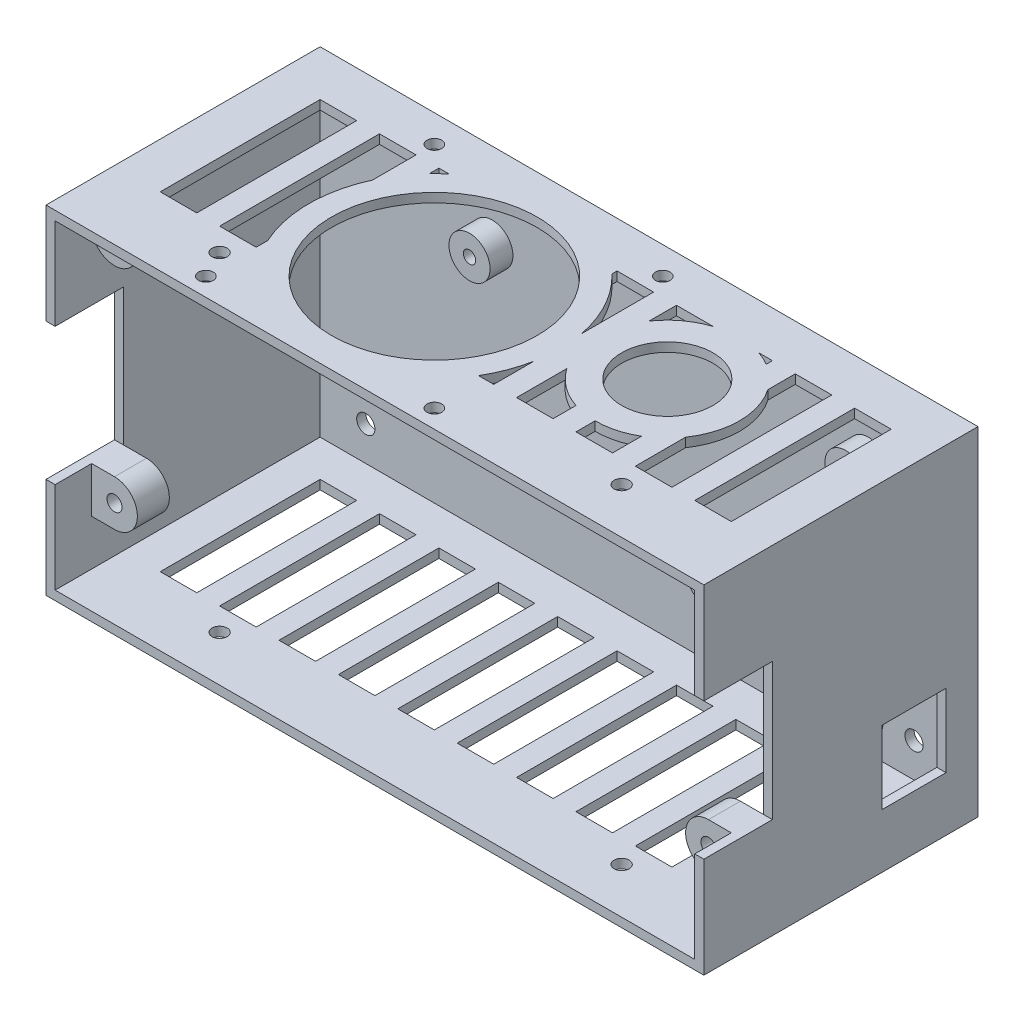
SolidWorks part; units mm, degrees
note: The reader was unsure of these and kept them because the rebuilt part matched: shared geometry of "Esboço8<3>", "Esboço13<3>", "Esboço15<3>".
material "ABS"
ref_plane "Plano frontal" through (0, 0, 0) normal (0, 0, 1) x (1, 0, 0)
ref_plane "Plano superior" through (0, 0, 0) normal (0, 1, 0) x (1, 0, 0)
ref_plane "Plano direito" through (0, 0, 0) normal (1, 0, 0) x (0, 0, -1)
sketch "Esboço1" plane through (0, 0, 0) normal (0, 0, 1) x (1, 0, 0)
  line L0 (-72, 37) -> (72, 37)
  line L1 (-70, 35) -> (70, 35)
  line L2 (-70, 35) -> (-70, -35)
  line L3 (-70, -35) -> (70, -35)
  line L4 (70, 35) -> (70, -35)
  line L5 (-70, 35) -> (70, -35) construction
  line L6 (-70, -35) -> (70, 35) construction
  line L7 (72, 37) -> (72, -37)
  line L8 (-72, -37) -> (72, -37)
  line L9 (-72, 37) -> (-72, -37)
  point P0 (0, 0)
  dimension "D2" = 140
  dimension "D3" = 70
  dimension "D1" = 2
extrude "Ressalto-extrusão1" add sketch "Esboço1" along normal blind 60
sketch "Esboço2" plane through (0, 0, 0) normal (0, 0, -1) x (-1, 0, 0)
  line L0 (-72, -37) -> (-72, 37) construction
  line L1 (72, -37) -> (-72, -37) construction
  line L2 (-72, 37) -> (72, 37) construction
  line L3 (72, 37) -> (72, -37) construction
  line L4 (-72, -37) -> (-72, 37)
  line L5 (72, -37) -> (-72, -37)
  line L6 (-72, 37) -> (72, 37)
  line L7 (72, 37) -> (72, -37)
  line L8 (60, 27.5) -> (-60, 27.5) construction
  line L9 (-60, 27.5) -> (-60, -27.5) construction
  line L10 (-60, -27.5) -> (60, -27.5) construction
  line L11 (60, -27.5) -> (60, 27.5) construction
  line L12 (-70, -35) -> (-70, 35) construction
  line L13 (70, -35) -> (-70, -35) construction
  circle A0 centre (-60, -27.5) radius 2
  circle A1 centre (60, -27.5) radius 2
  circle A2 centre (60, 27.5) radius 2
  circle A3 centre (-60, 27.5) radius 2
  point P12 (0, 27.5)
  point P13 (0, 37)
  point P14 (-60, 0)
  point P15 (-72, 0)
  dimension "D1" = 4
  dimension "D2" = 10
  dimension "D3" = 7.5
extrude "Ressalto-extrusão2" add sketch "Esboço2" against normal blind 2
sketch "Esboço3" plane through (72, 0, 0) normal (1, 0, 0) x (0, 0, -1)
  line L0 (-60, -37) -> (0, -37) construction
  line L5 (-21, -9.1) -> (-7, -9.1)
  line L6 (-21, -9.1) -> (-21, -25.1)
  line L7 (-21, -25.1) -> (-7, -25.1)
  line L8 (-7, -9.1) -> (-7, -25.1)
  line L18 (0, -37) -> (0, 37) construction
  dimension "D1" = 16
  dimension "D2" = 14
  dimension "D3" = 11.9
  dimension "D4" = 7
extrude "USB + fonte" cut sketch "Esboço3" against normal blind 10
sketch "Esboço6" plane through (0, -37, 0) normal (0, -1, 0) x (1, 0, 0)
  line L0 (-72, 0) -> (72, 0) construction
  line L1 (-62, 45) -> (-54, 45)
  line L2 (-62, 45) -> (-62, 10)
  line L3 (-62, 10) -> (-54, 10)
  line L4 (-54, 45) -> (-54, 10)
  line L5 (-72, 60) -> (-72, 0) construction
  line L6 (-49, 45) -> (-41, 45)
  line L7 (-49, 45) -> (-49, 10)
  line L8 (-49, 10) -> (-41, 10)
  line L9 (-41, 45) -> (-41, 10)
  line L10 (-36, 45) -> (-28, 45)
  line L11 (-36, 45) -> (-36, 10)
  line L12 (-36, 10) -> (-28, 10)
  line L13 (-28, 45) -> (-28, 10)
  line L14 (-23, 45) -> (-15, 45)
  line L15 (-23, 45) -> (-23, 10)
  line L16 (-23, 10) -> (-15, 10)
  line L17 (-15, 45) -> (-15, 10)
  line L18 (-10, 45) -> (-2, 45)
  line L19 (-10, 45) -> (-10, 10)
  line L20 (-10, 10) -> (-2, 10)
  line L21 (-2, 45) -> (-2, 10)
  line L22 (3, 45) -> (11, 45)
  line L23 (3, 45) -> (3, 10)
  line L24 (3, 10) -> (11, 10)
  line L25 (11, 45) -> (11, 10)
  line L26 (16, 45) -> (24, 45)
  line L27 (16, 45) -> (16, 10)
  line L28 (16, 10) -> (24, 10)
  line L29 (24, 45) -> (24, 10)
  line L30 (29, 45) -> (37, 45)
  line L31 (29, 45) -> (29, 10)
  line L32 (29, 10) -> (37, 10)
  line L33 (37, 45) -> (37, 10)
  line L34 (72, 60) -> (72, 0) construction
  line L35 (-72, 60) -> (-72, 0) construction
  line L36 (-72, 60) -> (72, 60) construction
  line L37 (42, 45) -> (50, 45)
  line L38 (42, 45) -> (42, 10)
  line L39 (42, 10) -> (50, 10)
  line L40 (50, 45) -> (50, 10)
  line L41 (55, 45) -> (63, 45)
  line L42 (55, 45) -> (55, 10)
  line L43 (55, 10) -> (63, 10)
  line L44 (63, 45) -> (63, 10)
  circle A0 centre (-44, 50) radius 1.65
  circle A1 centre (44, 50) radius 1.65
  dimension "D8" = 3.3
  dimension "D1" = 8
  dimension "D2" = 35
  dimension "D4" = 10
  dimension "D3" = 10
  dimension "D6" = 28
  dimension "D7" = 28
  dimension "D9" = 10
  dimension "D5" = 10
extrude "saida de ar" cut sketch "Esboço6" against normal through all both and the other way through all
sketch "Esboço7" plane through (-72, 0, 0) normal (-1, 0, 0) x (0, 0, 1)
  line L0 (60, 37) -> (60, -37) construction
  line L1 (45, -15) -> (60, -15)
  line L2 (45, -15) -> (45, 15)
  line L3 (45, 15) -> (60, 15)
  line L4 (60, -15) -> (60, 15)
  line L5 (45, -15) -> (60, 15) construction
  line L6 (45, 15) -> (60, -15) construction
  point P0 (52.5, 0)
  point P7 (0, 0)
  dimension "D1" = 30
  dimension "D2" = 15
extrude "display" cut sketch "Esboço7" against normal through all
sketch "Esboço8" plane through (0, 0, 2) normal (0, 0, -1) x (-1, 0, 0)
  line L0 (-70, -35) -> (-70, 35) construction
  line L1 (-70, 35) -> (70, 35) construction
  circle A0 centre (-48.7, -27.67) radius 4.5
  circle A1 centre (-48.7, -27.67) radius 1.35
  circle A2 centre (32.3, 20.5) radius 4.5
  circle A3 centre (32.3, 20.5) radius 1.35
  circle A4 centre (-50, 20.5) radius 1.35
  circle A5 centre (-50, 20.5) radius 1.35
  circle A6 centre (-50, 20.5) radius 4.5
  dimension "D1" = 9
  dimension "D2" = 2.7
  dimension "D3" = 82.3
  dimension "D4" = 48.17
  dimension "D5" = 1.3
  dimension "D6" = 20
  dimension "D7" = 14.5
extrude "Ressalto-extrusão3" add sketch "Esboço8" against normal blind 5 contours A2 A3 | A6 A4 | A0 A1
extrude "Corte-extrusão4" cut sketch "Esboço8<3>" along normal through all contours A4 | A3 | A1
sketch "Esboço8<3>" plane through (0, 0, 2) normal (0, 0, -1) x (-1, 0, 0) same geometry as "Esboço8"
sketch "Esboço9" plane through (0, 0, 2) normal (0, 0, 1) x (1, 0, 0)
  circle A0 centre (50, 20.5) radius 3
  circle A1 centre (48.7, -27.67) radius 3
  circle A2 centre (-32.3, 20.5) radius 3
  circle A3 centre (48.7, -27.67) radius 1.35 construction
  dimension "D1" = 6
extrude "Corte-extrusão5" cut sketch "Esboço9" along normal offset from surface 3 and the other way blind 10 up to face at (-27.8, 20.5, 7)
sketch "Esboço11" plane through (0, 0, 60) normal (0, 0, 1) x (1, 0, 0)
  line L0 (-70, 35) -> (-70, 15) construction
  line L1 (70, -25) -> (65, -25)
  line L2 (70, -25) -> (70, -15)
  line L3 (70, 35) -> (65, 35)
  line L4 (-70, -25) -> (-70, -15)
  line L5 (70, -25) -> (-70, 35) construction
  line L6 (70, 35) -> (-70, -25) construction
  line L7 (-72, 37) -> (-72, 15) construction
  line L8 (65, 30) -> (-65, 30) construction
  line L9 (65, 30) -> (65, -20) construction
  line L10 (65, -20) -> (-65, -20) construction
  line L11 (-65, 30) -> (-65, -20) construction
  line L12 (65, 30) -> (-65, -20) construction
  line L13 (65, -20) -> (-65, 30) construction
  line L14 (72, 37) -> (-72, 37) construction
  line L15 (-65, 35) -> (-70, 35)
  line L16 (-70, 30) -> (-70, 35)
  line L17 (70, 30) -> (70, 35)
  line L18 (-65, -25) -> (-70, -25)
  line L19 (70, -35) -> (70, -15) construction
  line L20 (-65, -15) -> (-70, -15)
  line L21 (-70, 35) -> (-70, -35) construction
  line L22 (65, -15) -> (70, -15)
  line L23 (70, -35) -> (70, 35) construction
  arc A0 (-70, 30) -> (-65, 35) centre (-65, 30) ccw
  circle A1 centre (-65, 30) radius 1.65
  arc A2 (65, 35) -> (70, 30) centre (65, 30) ccw
  circle A3 centre (65, 30) radius 1.65
  circle A5 centre (65, -20) radius 1.65
  arc A6 (-65, -25) -> (-65, -15) centre (-65, -20) ccw
  circle A7 centre (-65, -20) radius 1.65
  arc A8 (65, -15) -> (65, -25) centre (65, -20) ccw
  point P0 (0, 0)
  point P10 (0, 0)
  dimension "D3" = 3.3
  dimension "D1" = 7
  dimension "D2" = 7
  dimension "D5" = 50
  dimension "D4" = 5
extrude "Ressalto-extrusão4" add sketch "Esboço11" against normal blind 7 from offset 8 offset against normal yes
sketch "Esboço12" plane through (0, 0, 45) normal (0, 0, -1) x (-1, 0, 0)
  line L1 (-61.8246, 30) -> (-63.4123, 32.75)
  line L2 (-63.4123, 32.75) -> (-66.5877, 32.75)
  line L3 (-66.5877, 32.75) -> (-68.1754, 30)
  line L4 (-68.1754, 30) -> (-66.5877, 27.25)
  line L5 (-66.5877, 27.25) -> (-63.4123, 27.25)
  line L6 (-63.4123, 27.25) -> (-61.8246, 30)
  line L7 (61.8246, 30) -> (63.4123, 27.25)
  line L8 (63.4123, 27.25) -> (66.5877, 27.25)
  line L9 (66.5877, 27.25) -> (68.1754, 30)
  line L10 (68.1754, 30) -> (66.5877, 32.75)
  line L11 (66.5877, 32.75) -> (63.4123, 32.75)
  line L12 (63.4123, 32.75) -> (61.8246, 30)
  line L13 (-61.8246, -20) -> (-63.4123, -17.25)
  line L14 (-63.4123, -17.25) -> (-66.5877, -17.25)
  line L15 (-66.5877, -17.25) -> (-68.1754, -20)
  line L16 (-68.1754, -20) -> (-66.5877, -22.75)
  line L17 (-66.5877, -22.75) -> (-63.4123, -22.75)
  line L18 (-63.4123, -22.75) -> (-61.8246, -20)
  line L19 (61.8246, -20) -> (63.4123, -22.75)
  line L20 (63.4123, -22.75) -> (66.5877, -22.75)
  line L21 (66.5877, -22.75) -> (68.1754, -20)
  line L22 (68.1754, -20) -> (66.5877, -17.25)
  line L23 (66.5877, -17.25) -> (63.4123, -17.25)
  line L24 (63.4123, -17.25) -> (61.8246, -20)
  circle A0 centre (-65, 30) radius 2.75 construction
  circle A1 centre (65, 30) radius 2.75 construction
  circle A2 centre (-65, -20) radius 2.75 construction
  circle A3 centre (65, -20) radius 2.75 construction
  dimension "D1" = 5.5
extrude "Corte-extrusão6" cut sketch "Esboço12" against normal blind 3
sketch "Esboço13" plane through (0, 37, 0) normal (0, 1, 0) x (1, 0, 0)
  line L0 (72, -60) -> (72, 0) construction
  line L1 (72, 0) -> (-72, 0) construction
  circle A0 centre (29, -25) radius 10
  circle A2 centre (29, -25) radius 15.8114
  dimension "D3" = 20
  dimension "D1" = 43
  dimension "D2" = 25
extrude "Ressalto-extrusão5" add sketch "Esboço13" against normal blind 2
extrude "Corte-extrusão7" cut sketch "Esboço13<3>" against normal blind 10 contours A0
sketch "Esboço13<3>" plane through (0, 37, 0) normal (0, 1, 0) x (1, 0, 0) same geometry as "Esboço13"
sketch "Esboço15" plane through (0, 37, 0) normal (0, 1, 0) x (1, 0, 0)
  line L0 (72, -60) -> (-72, -60) construction
  line L1 (-41, -6) -> (9, -6) construction
  line L2 (-41, -6) -> (-41, -56) construction
  line L3 (-41, -56) -> (9, -56) construction
  line L4 (9, -6) -> (9, -56) construction
  line L5 (-41, -6) -> (9, -56) construction
  line L6 (-41, -56) -> (9, -6) construction
  circle A0 centre (-16, -31) radius 22.5
  circle A1 centre (-41, -56) radius 1.6
  circle A2 centre (9, -56) radius 1.6
  circle A3 centre (-41, -6) radius 1.6
  circle A4 centre (9, -6) radius 1.6
  circle A5 centre (29, -25) radius 10 construction
  circle A6 centre (-16, -31) radius 27.5
  dimension "D1" = 45
  dimension "D3" = 3.2
  dimension "D6" = 5
  dimension "D2" = 50
  dimension "D4" = 10
  dimension "D5" = 4
extrude "Corte-extrusão9" cut sketch "Esboço15" against normal blind 10 contours A0 | A4 | A3 | A1 | A2
extrude "Ressalto-extrusão6" add sketch "Esboço15<3>" against normal up to surface (2 mm away) contours A6 A0 up to face at (9, 35, 54.4)
sketch "Esboço15<3>" plane through (0, 37, 0) normal (0, 1, 0) x (1, 0, 0) same geometry as "Esboço15"
equation "\"D2@Esboço11\"=\"D1@Esboço11\""
equation "\"D7@Esboço6\"=\"D6@Esboço6\""
